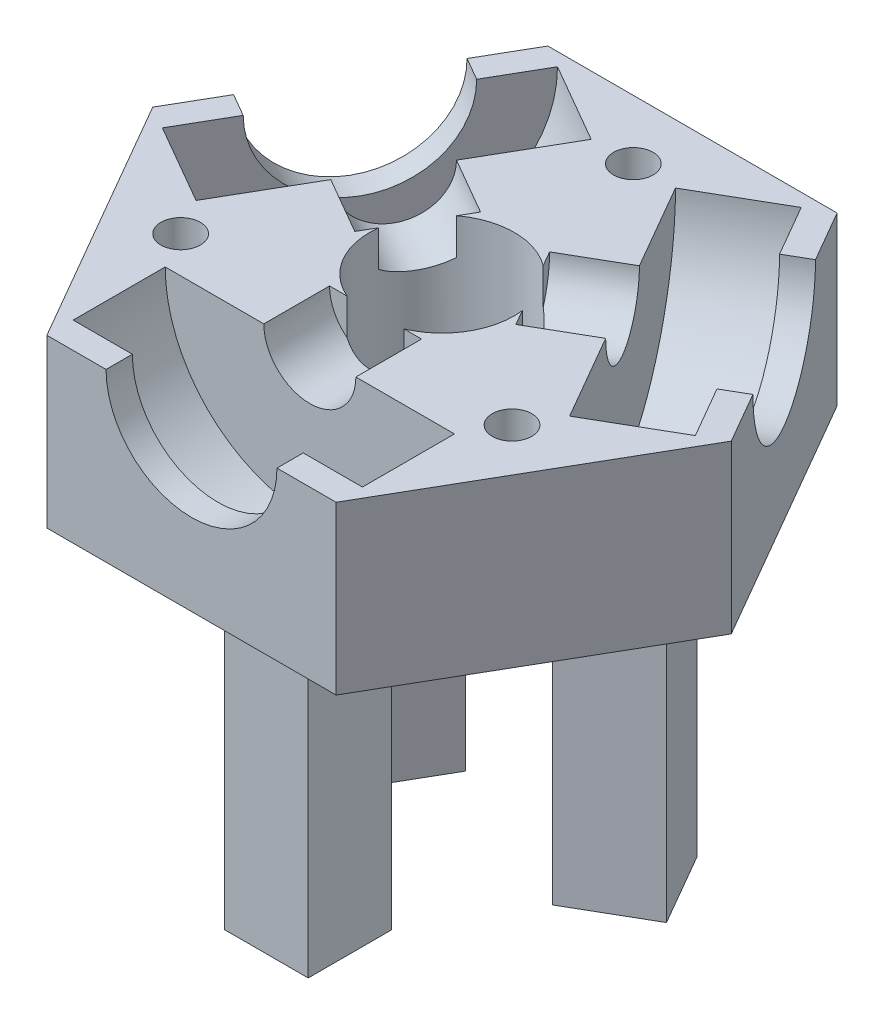
SolidWorks part; units mm, degrees
ref_plane "Front Plane" through (0, 0, 0) normal (0, 0, 1) x (1, 0, 0)
ref_plane "Top Plane" through (0, 0, 0) normal (0, 1, 0) x (1, 0, 0)
ref_plane "Right Plane" through (0, 0, 0) normal (1, 0, 0) x (0, 0, -1)
sketch "Sketch1" plane through (0, 0, 0) normal (0, 1, 0) x (1, 0, 0)
  line L1 (11, -19.0526) -> (22, 0)
  line L2 (22, 0) -> (11, 19.0526)
  line L3 (11, 19.0526) -> (-11, 19.0526)
  line L4 (-11, 19.0526) -> (-22, 0)
  line L5 (-22, 0) -> (-11, -19.0526)
  line L6 (-11, -19.0526) -> (11, -19.0526)
  circle A0 centre (0, 0) radius 19.0526 construction
  dimension "D1" = 22
extrude "Boss-Extrude1" add sketch "Sketch1" along normal blind 12.7 contours L4 L5 L6 L1 L2 L3
sketch "Sketch2" plane through (0, 0, 0) normal (0, -1, 0) x (1, 0, 0)
  circle A0 centre (0, 0) radius 5.5
  circle A1 centre (0, 0) radius 8.5
  dimension "D1" = 11
  dimension "D2" = 3
extrude "Boss-Extrude2" add sketch "Sketch2" along normal blind 3.5
sketch "Sketch4" plane through (0, 0, 0) normal (0, -1, 0) x (1, 0, 0)
  line L0 (13.1489, -3.9254) -> (7.6497, -0.7504)
  line L1 (-3.175, 13.35) -> (3.175, 13.35)
  line L2 (-3.175, 13.35) -> (-3.175, 7)
  line L3 (-3.175, 7) -> (3.175, 7)
  line L4 (3.175, 13.35) -> (3.175, 7)
  line L5 (-3.175, 13.35) -> (3.175, 7) construction
  line L6 (-3.175, 7) -> (3.175, 13.35) construction
  line L7 (13.1489, -3.9254) -> (9.9739, -9.4246)
  line L8 (9.9739, -9.4246) -> (4.4747, -6.2496)
  line L9 (7.6497, -0.7504) -> (4.4747, -6.2496)
  line L10 (-9.9739, -9.4246) -> (-4.4747, -6.2496)
  line L11 (-9.9739, -9.4246) -> (-13.1489, -3.9254)
  line L12 (-13.1489, -3.9254) -> (-7.6497, -0.7504)
  line L13 (-4.4747, -6.2496) -> (-7.6497, -0.7504)
  circle A1 centre (0, 0) radius 5.5 construction
  circle A2 centre (0, 0) radius 5.5 construction
  point P0 (0, 10.175)
  point P18 (0, 0)
  dimension "D1" = 6.35
  dimension "D2" = 1.5
  dimension "D4" = 1.5
  dimension "D5" = 1.5
  dimension "D3" = 3
extrude "Boss-Extrude4" add sketch "Sketch4" along normal blind 25.4
sketch "Sketch5" plane through (0, 12.7, 0) normal (0, 1, 0) x (1, 0, 0)
  line L14 (0, -19.0526) -> (0, -5.0526)
  line L15 (-11, -19.0526) -> (11, -19.0526) construction
  line L16 (0, -5.0526) -> (-3.5, -5.0526)
  line L17 (-3.5, -5.0526) -> (-3.5, -10.0526)
  line L18 (-3.5, -10.0526) -> (-11, -10.0526)
  line L19 (-11, -10.0526) -> (-11, -17.0526)
  line L20 (-11, -17.0526) -> (-6.5, -17.0526)
  line L21 (-6.5, -17.0526) -> (-6.5, -19.0526)
  line L22 (-6.5, -19.0526) -> (0, -19.0526)
  dimension "D1" = 6.5
  dimension "D2" = 11
  dimension "D3" = 2
  dimension "D4" = 7
  dimension "D5" = 5
  dimension "D6" = 3.5
revolve "Cut-Revolve1" cut sketch "Sketch5" angle 360 about L14
pattern_circular "CirPattern1" count 3 over 360 about axis through (0, -3.5, 0) along (0, 1, 0) of "Cut-Revolve1" reverse direction yes
sketch "Sketch6" plane through (0, 12.7, 0) normal (0, 1, 0) x (1, 0, 0)
  circle A0 centre (0, 0) radius 5.5
  dimension "D1" = 11
extrude "Cut-Extrude1" cut sketch "Sketch6" against normal through all
sketch "Sketch7" plane through (0, 12.7, 0) normal (0, 1, 0) x (1, 0, 0)
  line L0 (11, 19.0526) -> (-11, 19.0526) construction
  line L1 (-22, 0) -> (-11, -19.0526) construction
  line L2 (11, -19.0526) -> (22, 0) construction
  circle A0 centre (0, 14.5526) radius 1.5
  circle A1 centre (12.6029, -7.2763) radius 1.5
  circle A2 centre (-12.6029, -7.2763) radius 1.5
  point P11 (0, 0)
  dimension "D1" = 3
  dimension "D2" = 3
  dimension "D4" = 3
  dimension "D5" = 3
  dimension "D3" = 3
extrude "Cut-Extrude2" cut sketch "Sketch7" against normal up to surface (12.7 mm away) up to face at (0, 0, 0)
